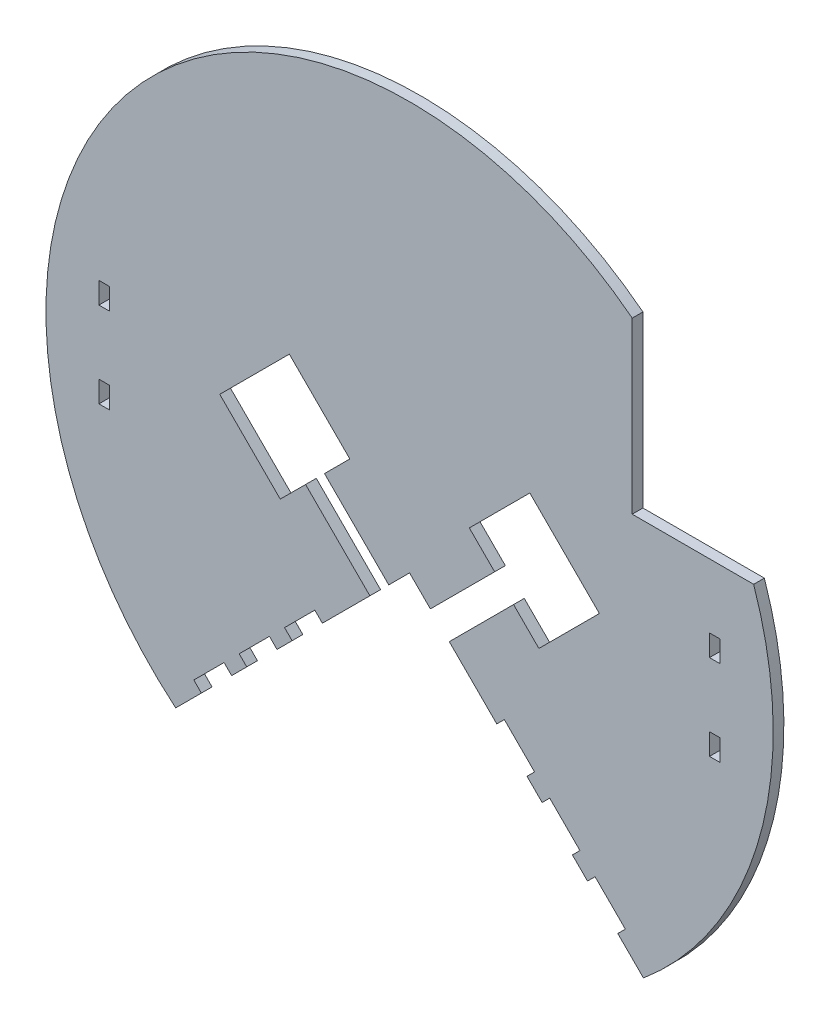
SolidWorks part; units mm, degrees
ref_plane "Front Plane" through (0, 0, 0) normal (0, 0, 1) x (1, 0, 0)
ref_plane "Top Plane" through (0, 0, 0) normal (0, 1, 0) x (1, 0, 0)
ref_plane "Right Plane" through (0, 0, 0) normal (1, 0, 0) x (0, 0, -1)
sketch "Sketch1" plane through (0, 0, 0) normal (0, 0, 1) x (1, 0, 0)
  circle A0 centre (0, 0) radius 215.9
  arc A1 (209.8384, 50.8) -> (202.0059, 76.2) centre (0, 0) ccw construction
extrude "Boss-Extrude1" add sketch "Sketch1" along normal blind 6.35 contours A0
sketch "Sketch2" plane through (0, 0, 0) normal (0, 0, -1) x (-1, 0, 0)
  line L0 (0, -26.4411) -> (138.8703, -165.3114)
  line L2 (0, -26.4411) -> (-138.8703, -165.3114)
  line L3 (-49.2431, -75.6842) -> (0, -26.4411) construction
  line L4 (0, 0) -> (0, -240.5018) construction
  arc A4 (-138.8703, -165.3114) -> (138.8703, -165.3114) centre (0, 0) ccw
  circle A5 centre (0, 0) radius 215.9 construction
  dimension "D1" = 90
extrude "Cut-Extrude1" cut sketch "Sketch2" against normal through all
sketch "Sketch3" plane through (0, 0, 6.35) normal (0, 0, 1) x (1, 0, 0)
  line L0 (71.393, 50.3401) -> (112.7022, 9.0309)
  line L1 (71.393, 50.3401) -> (35.472, 14.4191)
  line L2 (112.7022, 9.0309) -> (76.7812, -26.8901)
  line L3 (35.472, 14.4191) -> (76.7812, -26.8901)
  line L4 (76.7812, -26.8901) -> (72.2911, -22.4) construction
  line L5 (97.2507, 34.8885) -> (46.1575, -16.2046) construction
  line L6 (50.5139, -0.6229) -> (61.7393, -11.8482)
  line L7 (50.5139, -0.6229) -> (12.3479, -38.7889)
  line L8 (61.7393, -11.8482) -> (23.5732, -50.0143)
  line L9 (12.3479, -38.7889) -> (23.5732, -50.0143)
  line L10 (88.68, 15.0926) -> (77.4547, 26.3179) construction
  line L11 (0, -26.4411) -> (138.8703, -165.3114) construction
  line M8 (0, -26.4411) -> (138.8703, -165.3114)
extrude "Cut-Extrude2" cut sketch "Sketch3" against normal through all contours L8 L6 L3 L7 M8 | L0 L5 L6 L3 L2 | L5 L0 L1 L3 region at (63.7598, 22.0523, 6.35) region at (84.4144, 1.3977, 6.35) region at (37.0436, -25.3186, 6.35)
mirror "Mirror1" about plane through (0, 0, 0) normal (1, 0, 0) of "Cut-Extrude2"
sketch "Sketch4" plane through (0, 0, 6.35) normal (0, 0, 1) x (1, 0, 0)
  line L0 (-178.0884, 19.05) -> (-178.0884, 31.75) construction
  line L1 (178.0884, -19.05) -> (184.4384, -19.05)
  line L2 (178.0884, -19.05) -> (178.0884, -31.75)
  line L3 (178.0884, -31.75) -> (184.4384, -31.75)
  line L4 (184.4384, -19.05) -> (184.4384, -31.75)
  line L5 (178.0884, 31.75) -> (184.4384, 31.75)
  line L6 (178.0884, 31.75) -> (178.0884, 19.05)
  line L7 (178.0884, 19.05) -> (184.4384, 19.05)
  line L8 (184.4384, 31.75) -> (184.4384, 19.05)
  line L9 (178.0884, -19.05) -> (184.4384, -19.05)
  line L10 (178.0884, -19.05) -> (178.0884, -31.75)
  line L11 (178.0884, -31.75) -> (184.4384, -31.75)
  line L12 (184.4384, -19.05) -> (184.4384, -31.75)
  line L13 (-184.4384, 31.75) -> (-178.0884, 31.75)
  line L14 (-184.4384, 31.75) -> (-184.4384, 19.05)
  line L15 (-184.4384, 19.05) -> (-178.0884, 19.05)
  line L16 (-178.0884, 31.75) -> (-178.0884, 19.05)
  line L18 (-184.4384, -19.05) -> (-178.0884, -19.05)
  line L19 (-184.4384, -19.05) -> (-184.4384, -31.75)
  line L20 (-184.4384, -31.75) -> (-178.0884, -31.75)
  line L21 (-178.0884, -19.05) -> (-178.0884, -31.75)
extrude "Cut-Extrude3" cut sketch "Sketch4" against normal through all contours L21 L18 L19 L20 | L8 L5 L6 L7 | L4 L1 L2 L3 | L14 L15 L16 L13 region at (181.2634, -25.4, 6.35) region at (181.2634, 25.4, 6.35) region at (-181.2634, -25.4, 6.35)
sketch "Sketch5" plane through (0, 0, 6.35) normal (0, 0, 1) x (1, 0, 0)
  line L0 (-128.1057, -145.5666) -> (-110.1452, -127.6061)
  line L1 (-110.1452, -127.6061) -> (-105.6551, -132.0962)
  line L2 (-138.8703, -165.3114) -> (-23.5732, -50.0143) construction
  line L3 (-105.6551, -132.0962) -> (-110.1452, -127.6061) construction
  line L4 (-105.6551, -132.0962) -> (-123.6156, -150.0567)
  line L5 (-128.1057, -145.5666) -> (-123.6156, -150.0567) construction
  line L6 (-123.6156, -150.0567) -> (-128.1057, -145.5666)
extrude "Cut-Extrude4" cut sketch "Sketch5" against normal blind 6.35
pattern_linear "LPattern1" count 3 spacing 38.1 along (0.7071, 0.7071, 0) of "Cut-Extrude4"
sketch "Sketch6" plane through (0, 0, 6.35) normal (0, 0, 1) x (1, 0, 0)
  line L0 (110.1452, -127.6061) -> (128.1057, -145.5666)
  line L1 (128.1057, -145.5666) -> (123.6156, -150.0567)
  line L2 (23.5732, -50.0143) -> (138.8703, -165.3114) construction
  line L3 (123.6156, -150.0567) -> (128.1057, -145.5666) construction
  line L4 (123.6156, -150.0567) -> (105.6551, -132.0962)
  line L5 (110.1452, -127.6061) -> (105.6551, -132.0962) construction
  line L6 (105.6551, -132.0962) -> (110.1452, -127.6061)
extrude "Cut-Extrude5" cut sketch "Sketch6" against normal blind 6.35
pattern_linear "LPattern2" count 3 spacing 38.1 along (-0.7071, 0.7071, 0) of "Cut-Extrude5"
sketch "Sketch7" plane through (0, 0, 6.35) normal (0, 0, 1) x (1, 0, 0)
  line L0 (204.2885, 69.85) -> (132.2121, 69.85)
  line L1 (132.2121, 69.85) -> (132.2121, 170.6832)
  line L2 (221.1121, 69.85) -> (132.2121, 69.85) construction
  line L3 (132.2121, 76.2) -> (132.2121, 152.4) construction
  arc A0 (138.8703, -165.3114) -> (-138.8703, -165.3114) centre (0, 0) ccw construction
  arc A1 (204.2885, 69.85) -> (132.2121, 170.6832) centre (0, 0) ccw
extrude "Cut-Extrude6" cut sketch "Sketch7" against normal up to surface (6.35 mm away) up to face at (181.2634, -25.4, 0)
